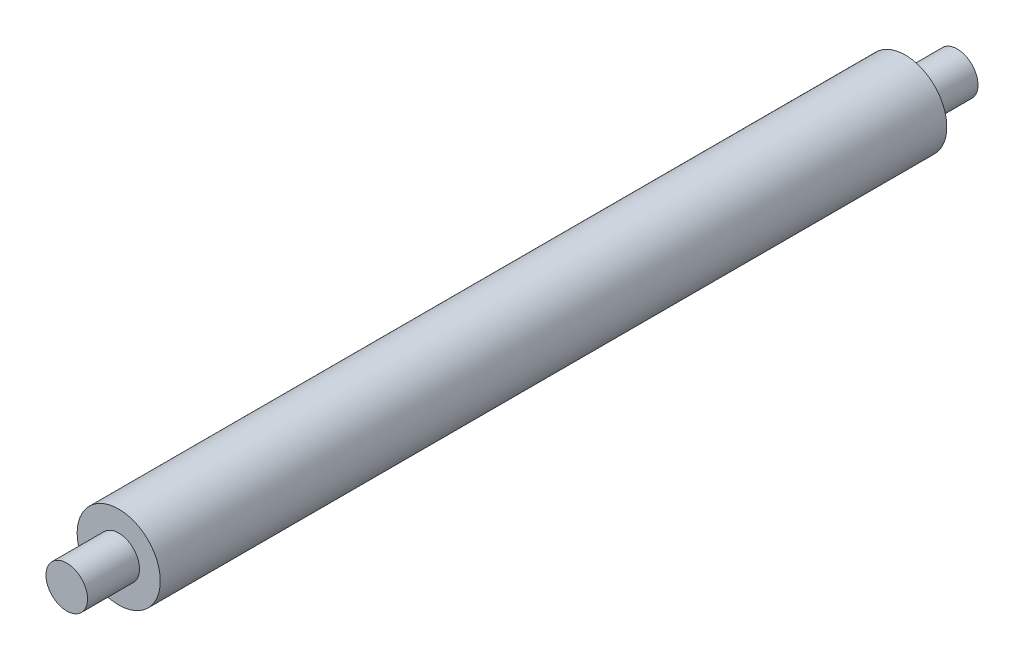
SolidWorks part; units mm, degrees
ref_plane "Front Plane" through (0, 0, 0) normal (0, 0, 1) x (1, 0, 0)
ref_plane "Top Plane" through (0, 0, 0) normal (0, 1, 0) x (1, 0, 0)
ref_plane "Right Plane" through (0, 0, 0) normal (1, 0, 0) x (0, 0, -1)
sketch "Sketch1" plane through (0, 0, 0) normal (0, 0, 1) x (1, 0, 0)
  circle A0 centre (0, 0) radius 6
  dimension "D1" = 12
extrude "Boss-Extrude1" add sketch "Sketch1" along normal mid plane 113.5
sketch "Sketch2" plane through (0, 0, 56.75) normal (0, 0, 1) x (1, 0, 0)
  circle A0 centre (0, 0) radius 3
  dimension "D1" = 6
extrude "Boss-Extrude2" add sketch "Sketch2" along normal blind 7.5
sketch "Sketch3" plane through (0, 0, -56.75) normal (0, 0, -1) x (-1, 0, 0)
  circle A0 centre (0, 0) radius 3
  dimension "D1" = 6
extrude "Boss-Extrude3" add sketch "Sketch3" along normal blind 7.5
